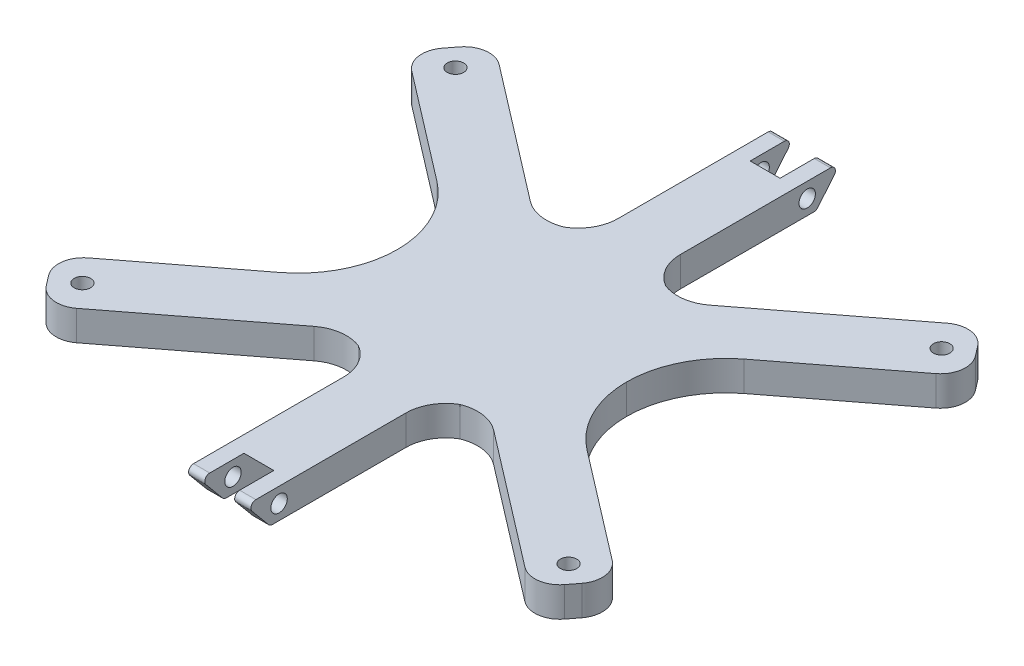
SolidWorks part; units mm, degrees
ref_plane "Front Plane" through (0, 0, 0) normal (0, 0, 1) x (1, 0, 0)
ref_plane "Top Plane" through (0, 0, 0) normal (0, 1, 0) x (1, 0, 0)
ref_plane "Right Plane" through (0, 0, 0) normal (1, 0, 0) x (0, 0, -1)
sketch "Sketch1" plane through (0, 0, 0) normal (0, 1, 0) x (1, 0, 0)
  circle A0 centre (0, 0) radius 23
  dimension "D1" = 46
extrude "Boss-Extrude1" add sketch "Sketch1" along normal blind 6
sketch "Sketch2" plane through (0, 0, 0) normal (0, 1, 0) x (1, 0, 0)
  line L0 (-21.3653, 8.5162) -> (-56.5628, 35.5242)
  line L1 (0.2695, -0.2068) -> (-63.7589, 48.924) construction
  line L2 (-48.9532, 45.4411) -> (-13.7557, 18.4331)
  line L3 (0, 37.6664) -> (0, -25.0328) construction
  line L4 (-48.9532, 45.4411) -> (-56.5628, 35.5242)
  circle A0 centre (0, 0) radius 23 construction
  arc A1 (-13.7557, 18.4331) -> (-21.3653, 8.5162) centre (0, 0) ccw
  point P9 (-52.758, 40.4826)
  dimension "D1" = 66.5
  dimension "D2" = 52.5
  dimension "D3" = 12.5
extrude "Boss-Extrude2" add sketch "Sketch2" along normal up to surface (6 mm away) up to face at (0, 6, 23)
mirror "Mirror1" about plane through (0, 0, 0) normal (1, 0, 0) of "Boss-Extrude2"
mirror "Mirror2" about plane through (0, 0, 0) normal (0, 0, 1) of "Mirror1", "Boss-Extrude2"
sketch "Sketch4" plane through (0, 6, 0) normal (0, 1, 0) x (1, 0, 0)
  line L0 (0, 65.599) -> (0, -44.8835) construction
  line L2 (-6.25, 59.8) -> (6.25, 59.8)
  line L4 (-6.25, 59.8) -> (-6.25, 22.1345)
  line L5 (6.25, 59.8) -> (6.25, 22.1345)
  arc A2 (13.7557, 18.4331) -> (-13.7557, 18.4331) centre (0, 0) ccw construction
  arc A3 (6.25, 22.1345) -> (-6.25, 22.1345) centre (0, 0) ccw
  point P8 (0, 59.8)
  dimension "D1" = 12.5
  dimension "D2" = 59.8
extrude "Boss-Extrude4" add sketch "Sketch4" against normal up to surface (6 mm away) up to face at (0, 0, 0)
mirror "Mirror6" about plane through (0, 0, 0) normal (0, 0, 1) of "Boss-Extrude4"
fillet "Fillet4" radius 8 8 edges at (-13.7557, 3, 18.4331) (-6.25, 3, 22.1345) (6.25, 3, 22.1345) (13.7557, 3, 18.4331) (13.7557, 3, -18.4331) (6.25, 3, -22.1345) (-6.25, 3, -22.1345) (-13.7557, 3, -18.4331)
fillet "Fillet5" radius 20 4 edges at (-21.3653, 3, 8.5162) (-21.3653, 3, -8.5162) (21.3653, 3, 8.5162) (21.3653, 3, -8.5162)
sketch "Sketch3" plane through (0, 6, 0) normal (0, 1, 0) x (1, 0, 0)
  circle A0 centre (-48.7912, 37.4388) radius 1.65
  dimension "D1" = 3.3
  dimension "D2" = 61.5
extrude "Cut-Extrude1" cut sketch "Sketch3" against normal through all
mirror "Mirror3" about plane through (0, 0, 0) normal (1, 0, 0) of "Cut-Extrude1"
mirror "Mirror4" about plane through (0, 0, 0) normal (0, 0, 1) of "Mirror3", "Cut-Extrude1"
sketch "Sketch13" plane through (-6.25, 0, 0) normal (-1, 0, 0) x (0, 0, 1)
  line L0 (-59.8, 0) -> (-59.8, 6) construction
  circle A0 centre (-53, 3) radius 1.65
  point P2 (-53, 4.9393)
  point P6 (-59.8, 3)
  dimension "D2" = 3.3
  dimension "D1" = 53
extrude "Cut-Extrude9" cut sketch "Sketch13" against normal blind 14
sketch "Sketch12" plane through (-6.25, 0, 0) normal (-1, 0, 0) x (0, 0, 1)
  line L0 (-59.8, 6) -> (-54.8, 0)
  line L2 (-54.8, 0) -> (-59.8, 0)
  line L3 (-59.8, 0) -> (-59.8, 6)
  line L4 (-27.5307, 0) -> (-59.8, 0) construction
  point P5 (0, 0)
  point P9 (-54.9707, 0)
  dimension "D1" = 5
extrude "Cut-Extrude8" cut sketch "Sketch12" against normal up to surface (12.5 mm away) up to face at (6.25, 3, -54.65)
sketch "Sketch14" plane through (0, 6, 0) normal (0, 1, 0) x (1, 0, 0)
  line L0 (-3, 59.8) -> (3, 59.8)
  line L1 (6.25, 59.8) -> (-6.25, 59.8) construction
  line L2 (3, 59.8) -> (3, 50.8)
  line L3 (3, 50.8) -> (-3, 50.8)
  line L4 (-3, 50.8) -> (-3, 59.8)
  point P4 (0, 50.8)
  dimension "D1" = 9
  dimension "D2" = 6
extrude "Cut-Extrude10" cut sketch "Sketch14" against normal blind 14
sketch "Sketch15" plane through (-3, 0, 0) normal (1, 0, 0) x (0, 0, -1)
  line L0 (50.8, 6) -> (40.4826, 0)
  line L1 (45.4411, 0) -> (35.5242, 0) construction
  line L2 (40.4826, 0) -> (50.8, 0)
  line L3 (50.8, 0) -> (50.8, 6)
extrude "Cut-Extrude11" cut sketch "Sketch15" along normal up to surface (6 mm away) up to face at (3, 3, -54.05)
mirror "Mirror8" about plane through (0, 0, 0) normal (0, 0, 1) of "Cut-Extrude11", "Cut-Extrude8", "Cut-Extrude9", "Cut-Extrude10"
fillet "Fillet3" radius 5 8 edges at (48.9532, 3, 45.4411) (56.5628, 3, 35.5242) (56.5628, 3, -35.5242) (48.9532, 3, -45.4411) (-48.9532, 3, -45.4411) (-56.5628, 3, -35.5242) (-56.5628, 3, 35.5242) (-48.9532, 3, 45.4411)
fillet "Fillet7" radius 1 8 edges at (4.625, 0, 54.8) (-4.625, 0, 54.8) (4.625, 6, 59.8) (-4.625, 6, 59.8) (-4.625, 0, -54.8) (4.625, 0, -54.8) (4.625, 6, -59.8) (-4.625, 6, -59.8)
